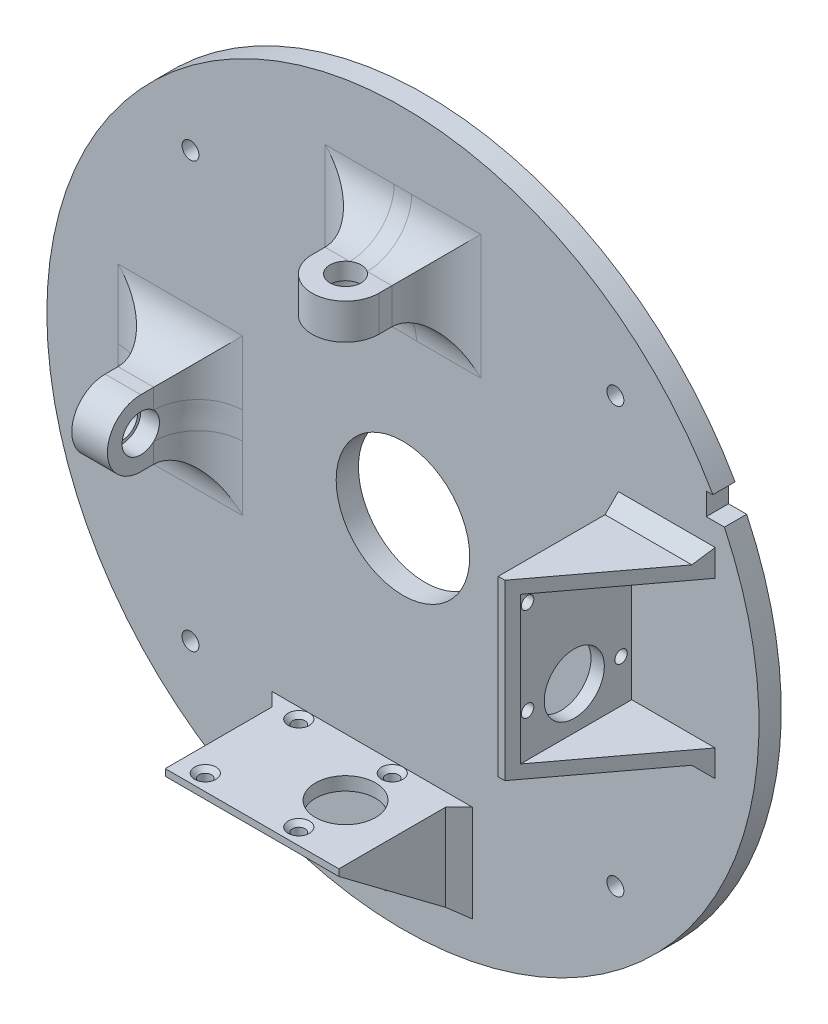
SolidWorks part; units mm, degrees
ref_plane "正面" through (0, 0, 0) normal (0, 0, 1) x (1, 0, 0)
ref_plane "平面" through (0, 0, 0) normal (0, 1, 0) x (1, 0, 0)
ref_plane "右側面" through (0, 0, 0) normal (1, 0, 0) x (0, 0, -1)
sketch "ｽｹｯﾁ5" plane through (0, 0, 0) normal (0, 1, 0) x (1, 0, 0)
  line L0 (48.4, -32) -> (48.4, 0)
  line L1 (48.4, 0) -> (72.4, 0)
  line L2 (72.4, 0) -> (48.4, -32)
  line L3 (-55, 0) -> (55, 0) construction
  point P5 (69.6322, 0)
  dimension "D1" = 24
  dimension "D2" = 32
  dimension "D3" = 48.4
extrude "ﾎﾞｽ - 押し出し3" add sketch "ｽｹｯﾁ5" against normal blind 39 from offset 26.4
shell "ｼｪﾙ2" thickness 3 removed face at (60.4, 6.9, 16)
sketch "ｽｹｯﾁ7" plane through (51.4, 0, 0) normal (1, 0, 0) x (0, 0, -1)
  line L0 (-3, -9.6) -> (-3, 23.4) construction
  line L1 (-26.4, 0) -> (-5.4, 0) construction
  line L2 (-26.4, 0) -> (-26.4, 21) construction
  line L3 (-26.4, 21) -> (-5.4, 21) construction
  line L4 (-5.4, 0) -> (-5.4, 21) construction
  line L5 (-3, 23.4) -> (-28, 23.4) construction
  circle A0 centre (-15.9, 0) radius 6.75
  circle A1 centre (-26.4, 0) radius 1.4
  circle A2 centre (-5.4, 0) radius 1.4
  circle A3 centre (-5.4, 21) radius 1.4
  circle A4 centre (-26.4, 21) radius 1.4
  point P10 (-15.9, 0)
  dimension "D3" = 2.8
  dimension "D6" = 13.5
  dimension "D1" = 21
  dimension "D2" = 21
  dimension "D4" = 2.4
  dimension "D5" = 2.4
extrude "ｶｯﾄ - 押し出し5" cut sketch "ｽｹｯﾁ7" against normal through all
sketch "ｽｹｯﾁ12" plane through (0, 0, 0) normal (0, 0, 1) x (1, 0, 0)
  line L0 (48.4, -12.6) -> (48.4, 26.4) construction
  line L1 (48.4, -12.6) -> (48.4, 26.4)
  line L2 (48.4, 26.4) -> (86.6023, 26.4)
  line L3 (72.4, 26.4) -> (48.4, 26.4) construction
  line L4 (86.6023, 26.4) -> (86.6023, -12.6)
  line L5 (86.6023, -12.6) -> (48.4, -12.6)
  line L6 (72.4, -12.6) -> (48.4, -12.6) construction
extrude "ｶｯﾄ - 押し出し14" cut sketch "ｽｹｯﾁ12" along normal blind 10 from offset 30
sketch "ｽｹｯﾁ18" plane through (48.4, 0, 0) normal (-1, 0, 0) x (0, 0, 1)
  circle A0 centre (26.4, 21) radius 2.4
  circle A1 centre (26.4, 0) radius 2.4
  circle A2 centre (5.4, 21) radius 2.4
  circle A3 centre (5.4, 0) radius 2.4
  dimension "D1" = 4.8
extrude "ｶｯﾄ - 押し出し15" cut sketch "ｽｹｯﾁ18" against normal blind 1.2 draft 45
sketch "ｽｹｯﾁ1" plane through (0, 0, 0) normal (0, 0, 1) x (1, 0, 0)
  line L1 (56.5685, -56.5685) -> (-56.5685, -56.5685) construction
  line L2 (56.5685, -56.5685) -> (56.5685, 56.5685) construction
  line L3 (56.5685, 56.5685) -> (-56.5685, 56.5685) construction
  line L4 (-56.5685, -56.5685) -> (-56.5685, 56.5685) construction
  line L5 (56.5685, -56.5685) -> (-56.5685, 56.5685) construction
  line L6 (56.5685, 56.5685) -> (-56.5685, -56.5685) construction
  circle A0 centre (0, 0) radius 80
  point P0 (0, 0)
  dimension "D1" = 160
extrude "ﾎﾞｽ - 押し出し1" add sketch "ｽｹｯﾁ1" along normal blind 3 and the other way blind 2 contours A0
sketch "ｽｹｯﾁ3" plane through (0, 0, 0) normal (0, 0, 1) x (1, 0, 0)
  circle A0 centre (0, 0) radius 15
  dimension "D1" = 30
extrude "ｶｯﾄ - 押し出し4" cut sketch "ｽｹｯﾁ3" against normal through all both and the other way through all
ref_plane "平面1" through (0, 54, 0) normal (0, 1, 0) x (1, 0, 0)
sketch "ｽｹｯﾁ10" plane through (-147.416, 54, 0) normal (0, 1, 0) x (1, 0, 0)
  line L0 (139.916, 0) -> (154.916, 0)
  line L1 (154.916, 0) -> (154.916, -15.9)
  line L2 (139.916, 0) -> (139.916, -15.9)
  line L3 (59.416, 0) -> (235.416, 0) construction
  arc A2 (139.916, -15.9) -> (154.916, -15.9) centre (147.416, -15.9) ccw
  point P7 (147.416, 0)
  dimension "D1" = 15
  dimension "D2" = 15.9
extrude "ﾎﾞｽ - 押し出し5" add sketch "ｽｹｯﾁ10" against normal blind 8
sketch "ｽｹｯﾁ11" plane through (-147.416, 54, 0) normal (0, 1, 0) x (1, 0, 0)
  circle A0 centre (147.416, -15.9) radius 4.2
  arc A1 (139.916, -15.9) -> (154.916, -15.9) centre (147.416, -15.9) ccw construction
  dimension "D1" = 8.4
extrude "ｶｯﾄ - 押し出し8" cut sketch "ｽｹｯﾁ11" along normal up to surface (-8 mm away) up to face at (0, 46, 11.325)
sketch "ｽｹｯﾁ14" plane through (0, 54, 0) normal (0, -1, 0) x (1, 0, 0)
  circle A0 centre (0, 15.9) radius 4.2 construction
  circle A1 centre (0, 15.9) radius 4.2
  circle A2 centre (0, 15.9) radius 3.5
  dimension "D1" = 7
extrude "ﾎﾞｽ - 押し出し6" add sketch "ｽｹｯﾁ14" along normal offset from surface (3.8 mm away) 4.2 up to face at (0, 46, 20.1)
fillet "ﾌｨﾚｯﾄ1" radius 10 4 edges at (7.5, 50, 3) (-7.5, 50, 3) (0, 46, 3) (0, 54, 3)
ref_plane "平面3" through (0, 0, 0) normal (0.7071, 0.7071, 0) x (-0.7071, 0.7071, 0)
mirror "ﾐﾗｰ1" about plane through (0, 0, 0) normal (0.7071, 0.7071, 0) of bodies 135 129
sketch "ｽｹｯﾁ15" plane through (0, 0, 3) normal (0, 0, 1) x (1, 0, 0)
  line L0 (-6.75, -51.4) -> (6.75, -51.4) construction
  line L1 (-3.85, -68.1) -> (-17.65, -68.1)
  line L2 (-3.85, -68.1) -> (-3.85, -74.4)
  line L3 (-3.85, -74.4) -> (-17.65, -74.4)
  line L4 (-17.65, -68.1) -> (-17.65, -74.4)
  line L5 (-3.85, -68.1) -> (-17.65, -74.4) construction
  line L6 (-3.85, -74.4) -> (-17.65, -68.1) construction
  line L7 (-6.75, -51.4) -> (6.75, -51.4)
  point P0 (-10.75, -71.25)
  point P7 (0, -51.4)
  dimension "D1" = 3.85
  dimension "D2" = 23
  dimension "D3" = 17.65
  dimension "D4" = 6.3
extrude "ｶｯﾄ - 押し出し11" cut sketch "ｽｹｯﾁ15" along normal through all both and the other way through all contours L1 L4 L3 L2 region at (-10.75, -71.25, 3)
sketch "ｽｹｯﾁ16" plane through (0, 0, 3) normal (0, 0, 1) x (1, 0, 0)
  line L0 (56.5685, 56.5685) -> (-56.5685, -56.5685) construction
  circle A0 centre (0, 0) radius 67.5 construction
  circle A1 centre (-47.7297, -47.7297) radius 1.9
  circle A3 centre (-47.7297, 47.7297) radius 1.9
  circle A4 centre (47.7297, 47.7297) radius 1.9
  circle A5 centre (47.7297, -47.7297) radius 1.9
  point P14 (0, 0)
  dimension "D1" = 135
  dimension "D3" = 3.8
  dimension "D2" = 4
extrude "ｶｯﾄ - 押し出し12" cut sketch "ｽｹｯﾁ16" against normal through all both and the other way through all
chamfer "面取り1" distance 3 angle 45 4 edges at (12.6, -59.275, 3) (-26.4, -59.275, 3) (59.275, 26.4, 3) (59.275, -12.6, 3)
sketch "ｽｹｯﾁ17" plane through (0, 0, 3) normal (0, 0, 1) x (1, 0, 0)
  line L1 (68.15, 34.4) -> (78.15, 34.4)
  line L2 (68.15, 34.4) -> (68.15, 39.4)
  line L3 (68.15, 39.4) -> (78.15, 39.4)
  line L4 (78.15, 34.4) -> (78.15, 39.4)
  line L5 (68.15, 34.4) -> (78.15, 39.4) construction
  line L6 (68.15, 39.4) -> (78.15, 34.4) construction
  line L7 (48.4, 29.4) -> (70.15, 29.4) construction
  line L8 (70.15, 29.4) -> (70.15, 23.4) construction
  point P0 (73.15, 36.9)
  dimension "D1" = 5
  dimension "D2" = 10
  dimension "D3" = 5
  dimension "D4" = 2
extrude "ｶｯﾄ - 押し出し13" cut sketch "ｽｹｯﾁ17" against normal blind 10
equation "\"D3@ｽｹｯﾁ5\"=45+3.4"
